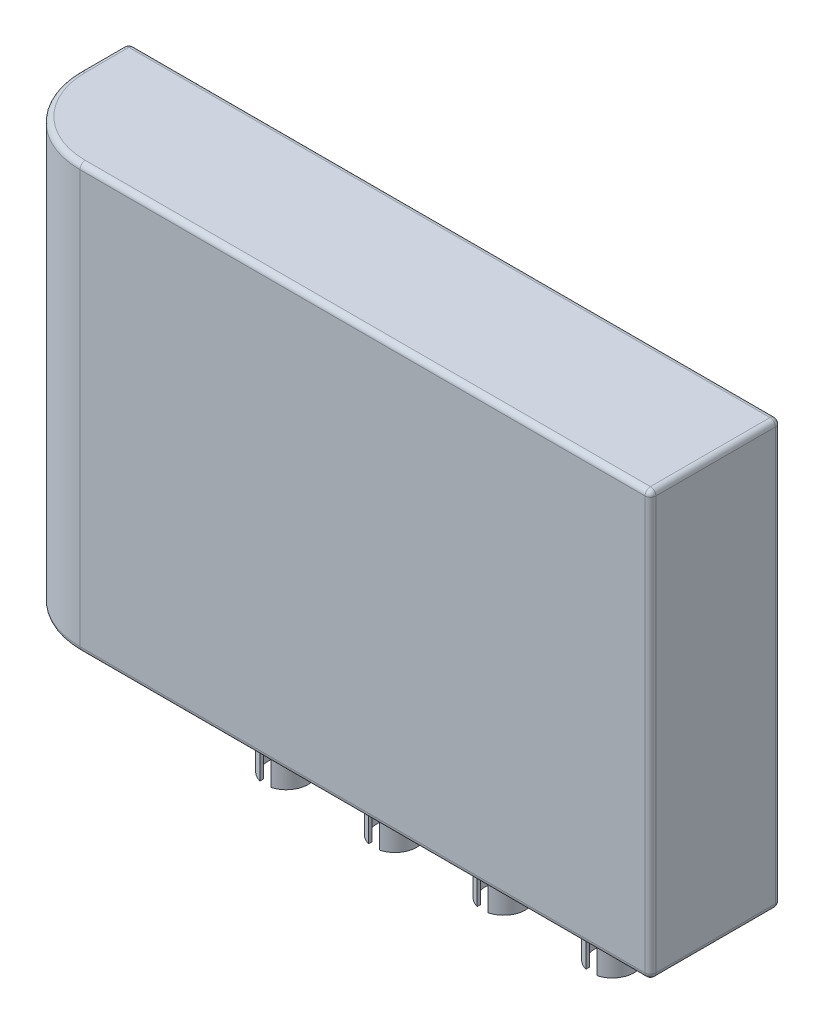
SolidWorks part; units mm, degrees
ref_plane "Front Plane" through (0, 0, 0) normal (0, 0, 1) x (1, 0, 0)
ref_plane "Top Plane" through (0, 0, 0) normal (0, 1, 0) x (1, 0, 0)
ref_plane "Right Plane" through (0, 0, 0) normal (1, 0, 0) x (0, 0, -1)
sketch "Sketch1" plane through (0, 0, 0) normal (0, 0, 1) x (1, 0, 0)
  line L1 (-60, -39) -> (60, -39)
  line L2 (-60, -39) -> (-60, 39)
  line L3 (-60, 39) -> (60, 39)
  line L4 (60, -39) -> (60, 39)
  line L5 (-60, -39) -> (60, 39) construction
  line L6 (-60, 39) -> (60, -39) construction
  point P0 (0, 0)
  dimension "D1" = 120
  dimension "D2" = 78
extrude "Boss-Extrude1" add sketch "Sketch1" along normal blind 24
fillet "Fillet1" radius 15 1 edges at (-60, 0, 24)
fillet "Fillet2" radius 1 13 edges at (-60, 39, 4.5) (7.5, 39, 24) (-55.6066, 39, 19.6066) (-60, -39, 4.5) (-55.6066, -39, 19.6066) (7.5, -39, 24) (0, 39, 0) (-60, 0, 0) (0, -39, 0) (60, -39, 12) (60, 0, 24) (60, 39, 12) (60, 0, 0)
ref_plane "Plane1" through (0, -39, 0) normal (0, -1, 0) x (-1, 0, 0)
sketch "Sketch2" plane through (0, -39, 0) normal (0, -1, 0) x (-1, 0, 0)
  line L0 (86.2195, -16) -> (-90.9173, -16) construction
  line L2 (60, -1) -> (60, -9) construction
  line L3 (16, -19.873) -> (16, -19.2496)
  line L4 (14, -19.873) -> (14, -19.2496)
  line L5 (14, -19.873) -> (16, -19.873) construction
  line L6 (-6, -19.873) -> (-6, -19.2496)
  line L7 (-4, -19.873) -> (-4, -19.2496)
  line L8 (-26, -19.873) -> (-26, -19.2496)
  line L9 (-24, -19.873) -> (-24, -19.2496)
  line L10 (-46, -19.873) -> (-46, -19.2496)
  line L11 (-44, -19.873) -> (-44, -19.2496)
  circle A0 centre (35, -16) radius 4
  circle A1 centre (15, -16) radius 4
  circle A2 centre (-5, -16) radius 4
  circle A3 centre (-25, -16) radius 4
  circle A4 centre (-45, -16) radius 4
  circle A5 centre (15, -16) radius 3.4
  circle A9 centre (-5, -16) radius 3.4
  circle A10 centre (-25, -16) radius 3.4
  circle A11 centre (-45, -16) radius 3.4
  point P16 (0, 0)
  point P23 (15, -19.873)
  dimension "D1" = 8
  dimension "D6" = 0.6
  dimension "D8" = 4
  dimension "D3" = 16
  dimension "D4" = 25
  dimension "D5" = 20
  dimension "D7" = 2
  dimension "D2" = 5
extrude "Boss-Extrude2" add sketch "Sketch2" along normal blind 8 contours A5 L3 A1 L4 | A9 L7 A2 L6 | A10 L9 A3 L8 | A11 L11 A4 L10 region at (-16.1122, -39, 19.5613) region at (7.3808, -39, 12.9265) region at (27.3808, -39, 12.9265) region at (47.3808, -39, 12.9265)
extrude "Cut-Extrude1" cut sketch "Sketch2<3>" against normal blind 8 contours A0 region at (-35, -39, 16)
sketch "Sketch2<3>" plane through (0, -39, 0) normal (0, -1, 0) x (-1, 0, 0) same geometry as "Sketch2"
